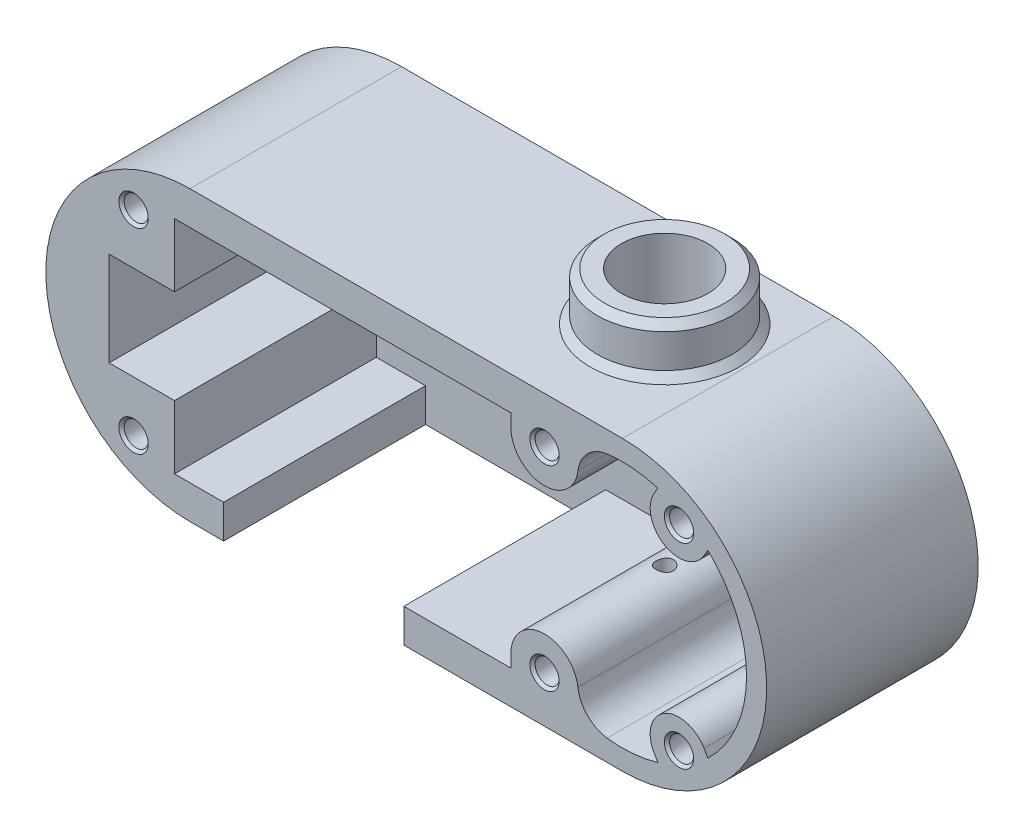
SolidWorks part; units mm, degrees
note: The reader was unsure of these and kept them because the rebuilt part matched: shared geometry of "Sketch2<3>".
ref_plane "Front" through (0, 0, 0) normal (0, 0, 1) x (1, 0, 0)
ref_plane "Top" through (0, 0, 0) normal (0, 1, 0) x (1, 0, 0)
ref_plane "Right" through (0, 0, 0) normal (1, 0, 0) x (0, 0, -1)
sketch "Sketch1" plane through (0, 0, 0) normal (0, 0, 1) x (1, 0, 0)
  line L0 (-36.885, 0) -> (8.115, 0) construction
  line L1 (-36.885, 15) -> (8.115, 15)
  line L2 (-36.885, -15) -> (8.115, -15)
  line L3 (13.99, 10.175) -> (13.99, -8.7693) construction
  line L4 (-14.385, 5.585) -> (-14.385, -8.7693) construction
  line L5 (-42.76, 10.175) -> (-42.76, -9.1693) construction
  line L6 (0, 10.175) -> (0, 0) construction
  line L7 (-42.76, 0) -> (-14.385, 0) construction
  arc A0 (-36.885, 15) -> (-36.885, -15) centre (-36.885, 0) ccw
  arc A1 (8.115, -15) -> (8.115, 15) centre (8.115, 0) ccw
  circle A2 centre (-42.76, 10.175) radius 1.25 construction
  circle A3 centre (13.99, 10.175) radius 1.25 construction
  circle A4 centre (0, 10.175) radius 1.25 construction
  circle A5 centre (13.99, -10.175) radius 1.25 construction
  circle A6 centre (0, -10.175) radius 1.25 construction
  circle A7 centre (-42.76, -10.175) radius 1.25 construction
  point P3 (-14.385, 0)
  dimension "D5" = 20.35
  dimension "D6" = 2.5
  dimension "D1" = 13.99
  dimension "D2" = 56.75
  dimension "D3" = 30
  dimension "D4" = 45
extrude "Boss-Extrude1" add sketch "Sketch1" along normal blind 25
sketch "Sketch2" plane through (0, 0, 25) normal (0, 0, 1) x (1, 0, 0)
  line L0 (-14.385, 0) -> (8.115, 0) construction
  line L1 (-38.5, 11.5) -> (-3.5, 11.5)
  line L2 (-3.5, 11.5) -> (-3.5, 10.175)
  line L3 (-36.885, 15) -> (8.115, 15) construction
  line L4 (-45.3, 4.9) -> (-45.3, -4.9)
  line L5 (-45.3, -4.9) -> (-38.5, -4.9)
  line L6 (-38.5, -4.9) -> (-38.5, -11.5)
  line L7 (-38.5, -11.5) -> (-33.385, -11.5)
  line L8 (-45.3, 4.9) -> (-38.5, 4.9)
  line L9 (-38.5, 4.9) -> (-38.5, 11.5)
  line L10 (-3.5, -11.5) -> (-3.5, -10.175)
  line L11 (16.588, 8.6749) -> (16.9866, 9.3651)
  line L12 (11.392, 11.6751) -> (11.7905, 12.3653)
  line L13 (8.115, 0) -> (13.99, 10.175) construction
  line L14 (16.588, -8.6749) -> (16.9866, -9.3651)
  line L15 (11.392, -11.6751) -> (11.7905, -12.3653)
  line L16 (-33.385, -11.5) -> (-33.385, -16.5)
  line L17 (-33.385, -16.5) -> (-14.635, -16.5)
  line L18 (-14.635, -16.5) -> (-14.635, -11.5)
  line L19 (-14.635, -11.5) -> (-3.5, -11.5)
  arc A0 (6.5141, 12.8003) -> (11.7905, 12.3653) centre (8.115, 0) cw
  arc A1 (11.392, 11.6751) -> (16.588, 8.6749) centre (13.99, 10.175) ccw
  arc A2 (11.392, -11.6751) -> (16.588, -8.6749) centre (13.99, -10.175) cw
  arc A3 (-3.5, 10.175) -> (3.4742, 9.7512) centre (0, 10.175) ccw
  arc A4 (3.4742, 9.7512) -> (6.5141, 12.8003) centre (6.9485, 9.3273) cw
  circle A5 centre (0, 10.175) radius 1.25 construction
  arc A6 (3.4742, -9.7512) -> (6.5141, -12.8003) centre (6.9485, -9.3273) ccw
  arc A7 (-3.5, -10.175) -> (3.4742, -9.7512) centre (0, -10.175) cw
  circle A8 centre (13.99, 10.175) radius 1.25 construction
  arc A9 (16.9866, 9.3651) -> (16.9866, -9.3651) centre (8.115, 0) cw
  arc A10 (11.7905, -12.3653) -> (6.5141, -12.8003) centre (8.115, 0) cw
  arc A11 (-1.7504, 7.1441) -> (-1.7504, -7.1441) centre (-5.8764, 0) cw
  dimension "D1" = 12.9
  dimension "D2" = 3.5
  dimension "D7" = 3
  dimension "D8" = 8.25
  dimension "D3" = 3.5
  dimension "D4" = 35
  dimension "D5" = 6.8
  dimension "D6" = 9.8
  dimension "D9" = 18.75
  dimension "D10" = 3.5
  dimension "D11" = 5
extrude "Cut-Extrude1" cut sketch "Sketch2" against normal blind 21 contours A11 A3 L2 L1 L9 L8 L4 L5 L6 L7 L10 A7
extrude "Cut-Extrude2" cut sketch "Sketch2<3>" against normal blind 16.25 contours A3 A11 A7 A6 A10 L15 A2 L14 A9 L11 A1 L12 A0 A4
sketch "Sketch2<3>" plane through (0, 0, 25) normal (0, 0, 1) x (1, 0, 0) same geometry as "Sketch2"
hole_wizard "M3 Tapped Hole1" positions "Sketch4" profile "Sketch3" tap size "M3" standard "ISO"
sketch "Sketch4" plane through (0, 0, 25) normal (0, 0, 1) x (1, 0, 0)
  point P0 (-42.76, 10.175)
  point P3 (-42.76, -10.175)
  point P6 (0, -10.175)
  point P9 (0, 10.175)
  point P12 (13.99, 10.175)
  point P15 (13.99, -10.175)
sketch "Sketch3" plane through (-42.76, 10.175, 25) normal (1, 0, 0) x (0, -1, 0)
  line L0 (0, 0) -> (0, 9.2511)
  line L1 (0, 9.2511) -> (1.25, 8.5)
  line L2 (1.25, 8.5) -> (1.25, 0.275)
  line L3 (1.25, 0.275) -> (1.525, 0)
  line L5 (1.525, 0) -> (0, 0)
  line L6 (-1.25, 0.275) -> (-1.525, 0) construction
  line L10 (0, 9.2511) -> (-1.25, 8.5) construction
  line L11 (0, -6.35) -> (0, 107.95) construction
  dimension "Tap Drill Dia." = 2.5
  dimension "Tap Drill Depth" = 8.5
  dimension "Near C'Sink Dia." = 3.05
  dimension "Near C'Sink Angle" = 90
  dimension "Drill Angle" = 118
cosmetic thread "Hole Thread1" parameters "D1"=6, "D2"=3
cosmetic thread "Hole Thread2" parameters "D1"=6, "D2"=3
cosmetic thread "Hole Thread3" parameters "D1"=6, "D2"=3
cosmetic thread "Hole Thread4" parameters "D1"=6, "D2"=3
cosmetic thread "Hole Thread5" parameters "D1"=6, "D2"=3
cosmetic thread "Hole Thread6" parameters "D1"=6, "D2"=3
sketch "Sketch5" plane through (0, 15, 0) normal (0, 1, 0) x (1, 0, 0)
  line L0 (8.115, 0) -> (-36.885, 0) construction
  circle A0 centre (0, -12.5) radius 7
  dimension "D1" = 14
  dimension "D2" = 12.5
extrude "Boss-Extrude2" add sketch "Sketch5" along normal blind 5
sketch "Sketch6" plane through (0, 20, 0) normal (0, 1, 0) x (1, 0, 0)
  circle A0 centre (0, -12.5) radius 4.5
  circle A1 centre (0, -12.5) radius 7 construction
  dimension "D1" = 9
extrude "Cut-Extrude3" cut sketch "Sketch6" against normal blind 7
sketch "Sketch7" plane through (0, 13, 0) normal (0, 1, 0) x (1, 0, 0)
  circle A0 centre (0, -12.5) radius 2.15
  circle A1 centre (0, -12.5) radius 4.5 construction
  dimension "D1" = 4.3
extrude "Cut-Extrude4" cut sketch "Sketch7" against normal blind 4.5
chamfer "Chamfer2" distance 1.5 distance2 3 1 edges at (-2.15, 13, 12.5)
sketch "Sketch8" plane through (0, 8.5, 0) normal (0, 1, 0) x (1, 0, 0)
  circle A0 centre (0, -12.5) radius 0.9
  dimension "D1" = 1.8
extrude "Cut-Extrude5" cut sketch "Sketch8" against normal up to next
mirror "Mirror1" about plane through (0, 0, 0) normal (0, 1, 0) of "Boss-Extrude2", "Cut-Extrude3", "Cut-Extrude4", "Chamfer2", "Cut-Extrude5"
chamfer "Chamfer3" distance 4.5 distance2 3 4 edges at (-51.885, 0, 0) (-14.385, -15, 0) (-14.385, 15, 0) (23.115, 0, 0)
chamfer "Chamfer4" distance 0.75 angle 45 4 edges at (-7, 20, 12.5) (7, 15, 12.5) (-7, -20, 12.5) (-7, -15, 12.5)
